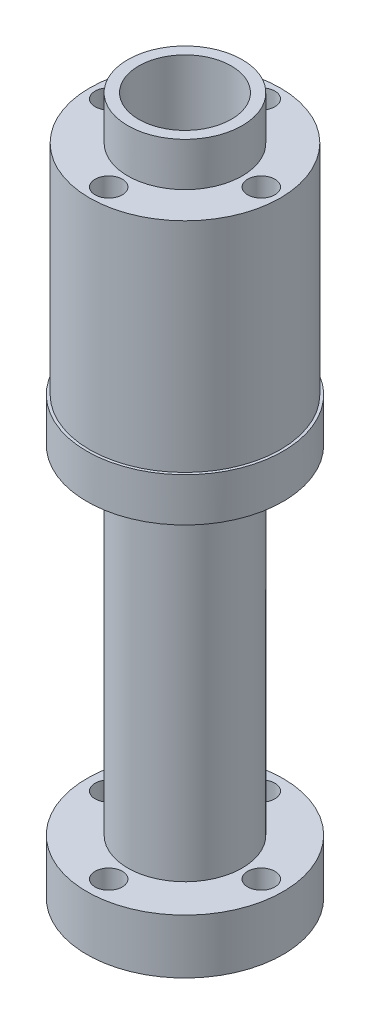
SolidWorks part; units mm, degrees
other "细节项目1"
other "细节项目2"
material "6061-T6 (SS)"
ref_plane "前视基准面" through (0, 0, 0) normal (0, 0, 1) x (1, 0, 0)
ref_plane "上视基准面" through (0, 0, 0) normal (0, 1, 0) x (1, 0, 0)
ref_plane "右视基准面" through (0, 0, 0) normal (1, 0, 0) x (0, 0, -1)
sketch "草图1" plane through (0, 0, 0) normal (0, 0, 1) x (1, 0, 0)
  line L0 (0, 0) -> (0, 22.2724) construction
  line L1 (-9, 36) -> (-5.25, 36)
  line L2 (-4.25, 0) -> (-9, 0)
  line L3 (-4.25, 0) -> (-4.25, 60)
  line L4 (-4.25, 60) -> (-9, 60)
  line L5 (-9, 0) -> (-9, 5)
  line L6 (-5.25, 36) -> (-5.25, 5)
  line L7 (-5.25, 5) -> (-9, 5)
  line L8 (-9, 36) -> (-9, 60)
  dimension "D1" = 8.5
  dimension "D2" = 18
  dimension "D3" = 60
  dimension "D4" = 36
  dimension "D5" = 5
  dimension "D6" = 1
revolve "旋转1" add sketch "草图1" angle 360 about L0
sketch "草图2" plane through (0, 60, 0) normal (0, 1, 0) x (1, 0, 0)
  circle A0 centre (0, 0) radius 7 construction
  circle A1 centre (0, 7) radius 1.25
  circle A2 centre (0, -7) radius 1.25
  circle A3 centre (-7, 0) radius 1.25
  circle A4 centre (7, 0) radius 1.25
  dimension "D1" = 14
  dimension "D2" = 2.5
extrude "切除-拉伸1" cut sketch "草图2" against normal blind 10
cosmetic thread "装饰螺纹线3" parameters "D2"=3
cosmetic thread "装饰螺纹线4" parameters "D2"=3
cosmetic thread "装饰螺纹线5" parameters "D2"=3
cosmetic thread "装饰螺纹线6" parameters "D2"=3
extrude "切除-拉伸2" cut sketch "草图2<2>" along normal blind 6 from surface starting at face at (0, 0, -4.25)
sketch "草图2<2>" plane through (0, 60, 0) normal (0, 1, 0) x (1, 0, 0) same geometry as "草图2"
cosmetic thread "装饰螺纹线1" parameters "D2"=3
cosmetic thread "装饰螺纹线2" parameters "D2"=3
cosmetic thread "装饰螺纹线7" parameters "D2"=3
cosmetic thread "装饰螺纹线8" parameters "D2"=3
sketch "草图3" plane through (0, 60, 0) normal (0, 1, 0) x (1, 0, 0)
  circle A0 centre (0, 0) radius 8.75
  dimension "D1" = 17.5
extrude "切除-拉伸3" cut sketch "草图3" against normal offset from surface (20 mm away) 4 flip side to cut up to face at (0, 36, -5.25)
sketch "草图4" plane through (0, 60, 0) normal (0, 1, 0) x (1, 0, 0)
  circle A0 centre (0, 0) radius 5.25
  circle A1 centre (0, 0) radius 4.25 construction
  circle A2 centre (0, 0) radius 4.25
  dimension "D1" = 10.5
extrude "凸台-拉伸1" add sketch "草图4" along normal blind 4
